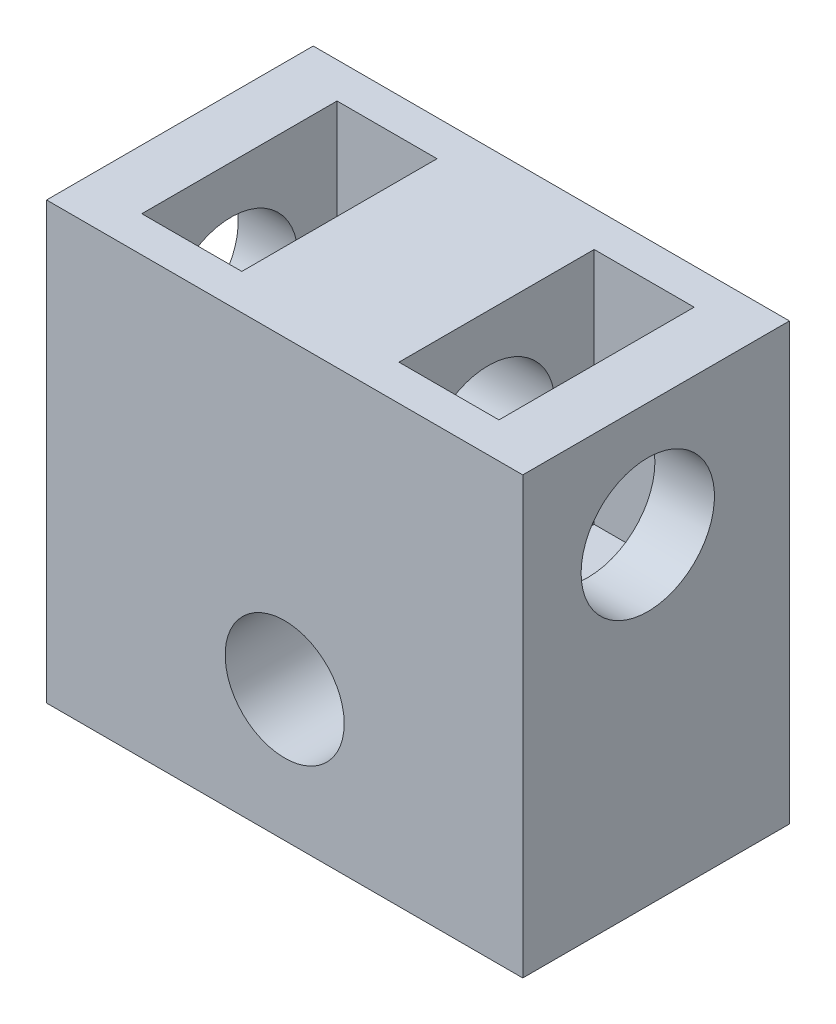
SolidWorks part; units mm, degrees
material "ABS PC"
ref_plane "Front Plane" through (0, 0, 0) normal (0, 0, 1) x (1, 0, 0)
ref_plane "Top Plane" through (0, 0, 0) normal (0, 1, 0) x (1, 0, 0)
ref_plane "Right Plane" through (0, 0, 0) normal (1, 0, 0) x (0, 0, -1)
sketch "Sketch6" plane through (0, 0, 0) normal (0, 1, 0) x (1, 0, 0)
  line L0 (0, 0) -> (0, 11.2)
  line L1 (0, 0) -> (20, 0)
  line L2 (0, 11.2) -> (20, 11.2)
  line L3 (20, 0) -> (20, 11.2)
  dimension "D1" = 20
  dimension "D2" = 11.2
extrude "Boss-Extrude2" add sketch "Sketch6" along normal blind 18.3
sketch "Sketch7" plane through (0, 0, 0) normal (0, 0, 1) x (1, 0, 0)
  line L0 (0, 0) -> (20, 0) construction
  line L1 (0, 18.3) -> (0, 0) construction
  circle A0 centre (10, 5.5) radius 2.5
  point P6 (9.3484, 5.0427)
  dimension "D1" = 5
  dimension "D2" = 5.5
  dimension "D3" = 10
extrude "Cut-Extrude4" cut sketch "Sketch7" against normal through all
sketch "Sketch8" plane through (0, 0, 0) normal (-1, 0, 0) x (0, 0, 1)
  line L1 (-11.2, 0) -> (0, 0) construction
  line L2 (0, 18.3) -> (0, 0) construction
  circle A0 centre (-5.25, 13.5) radius 2.8
  dimension "D1" = 5.6
  dimension "D3" = 13.5
  dimension "D2" = 5.25
extrude "Cut-Extrude5" cut sketch "Sketch8" against normal through all
sketch "Sketch9" plane through (0, 18.3, 0) normal (0, 1, 0) x (1, 0, 0)
  line L0 (2.5, 9.7) -> (6.7, 9.7)
  line L1 (2.5, 9.7) -> (2.5, 1.5)
  line L2 (6.7, 9.7) -> (6.7, 1.5)
  line L3 (2.5, 1.5) -> (6.7, 1.5)
  line L4 (13.3, 9.7) -> (17.5, 9.7)
  line L5 (13.3, 9.7) -> (13.3, 1.5)
  line L6 (17.5, 9.7) -> (17.5, 1.5)
  line L7 (13.3, 1.5) -> (17.5, 1.5)
  line L8 (0, 11.2) -> (0, 0) construction
  line L9 (20, 0) -> (20, 11.2) construction
  line L10 (20, 11.2) -> (0, 11.2) construction
  dimension "D1" = 1.5
  dimension "D2" = 4.2
  dimension "D3" = 2.5
  dimension "D4" = 2.5
  dimension "D5" = 8.2
extrude "Cut-Extrude6" cut sketch "Sketch9" against normal blind 10
